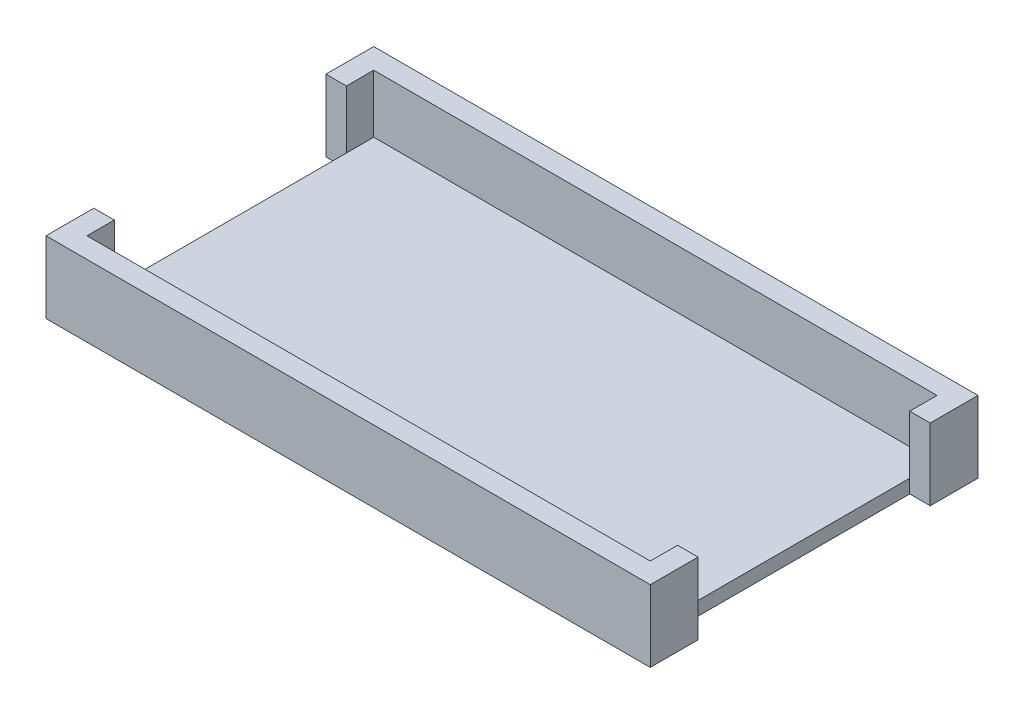
SolidWorks part; units mm, degrees
ref_plane "Front Plane" through (0, 0, 0) normal (0, 0, 1) x (1, 0, 0)
ref_plane "Top Plane" through (0, 0, 0) normal (0, 1, 0) x (1, 0, 0)
ref_plane "Right Plane" through (0, 0, 0) normal (1, 0, 0) x (0, 0, -1)
sketch "Sketch1" plane through (0, 0, 0) normal (0, 1, 0) x (1, 0, 0)
  line L0 (-22.125, 12) -> (-22.125, -12)
  line L1 (-20.625, 10.5) -> (20.625, 10.5)
  line L2 (-20.625, 10.5) -> (-20.625, -10.5)
  line L3 (-20.625, -10.5) -> (20.625, -10.5)
  line L4 (20.625, 10.5) -> (20.625, -10.5)
  line L5 (-20.625, 10.5) -> (20.625, -10.5) construction
  line L6 (-20.625, -10.5) -> (20.625, 10.5) construction
  line L7 (-22.125, -12) -> (22.125, -12)
  line L8 (22.125, 12) -> (22.125, -12)
  line L9 (-22.125, 12) -> (22.125, 12)
  line L10 (20.625, 0) -> (22.125, 0)
  line L11 (11.9112, 0) -> (20.625, 0)
  line L12 (16.2681, 8.5) -> (16.2681, -8.5)
  line L13 (16.2681, 8.5) -> (22.125, 8.5)
  line L14 (16.2681, -8.5) -> (22.125, -8.5)
  line L15 (0, -16.515) -> (0, 21.5864)
  line L16 (-16.2681, 8.5) -> (-16.2681, -8.5)
  line L17 (-16.2681, 8.5) -> (-22.125, 8.5)
  line L18 (-16.2681, -8.5) -> (-22.125, -8.5)
  point P0 (0, 0)
  point P15 (16.2681, 0)
  dimension "D1" = 41.25
  dimension "D2" = 21
  dimension "D4" = 17
  dimension "D3" = 1.5
extrude "Boss-Extrude1" add sketch "Sketch1" along normal blind 5.25 contours L15 L7 L8 L14 L4 L3 | L2 L18 L0 L7 L15 L3 | L17 L2 L1 L15 L9 L0 | L15 L1 L4 L13 L8 L9 region at (-11.9174, 0, -11.1049) region at (11.9174, 0, -11.1049) region at (-11.9174, 0, 11.1049) region at (11.9174, 0, 11.1049)
extrude "Boss-Extrude2" add sketch "Sketch1<2>" along normal blind 1 contours L15 L3 L4 L14 L12 L13 L1 | L16 L18 L2 L3 L15 L1 L17 | L12 L14 L4 L11 | L13 L12 L11 L4 | L18 L16 L17 L2 region at (-18.4466, 0, 0) region at (-8.6346, 0, 0) region at (8.6346, 0, 0) region at (18.4466, 0, -4.25) region at (18.4466, 0, 4.25)
sketch "Sketch1<2>" plane through (0, 0, 0) normal (0, 1, 0) x (1, 0, 0) same geometry as "Sketch1"
